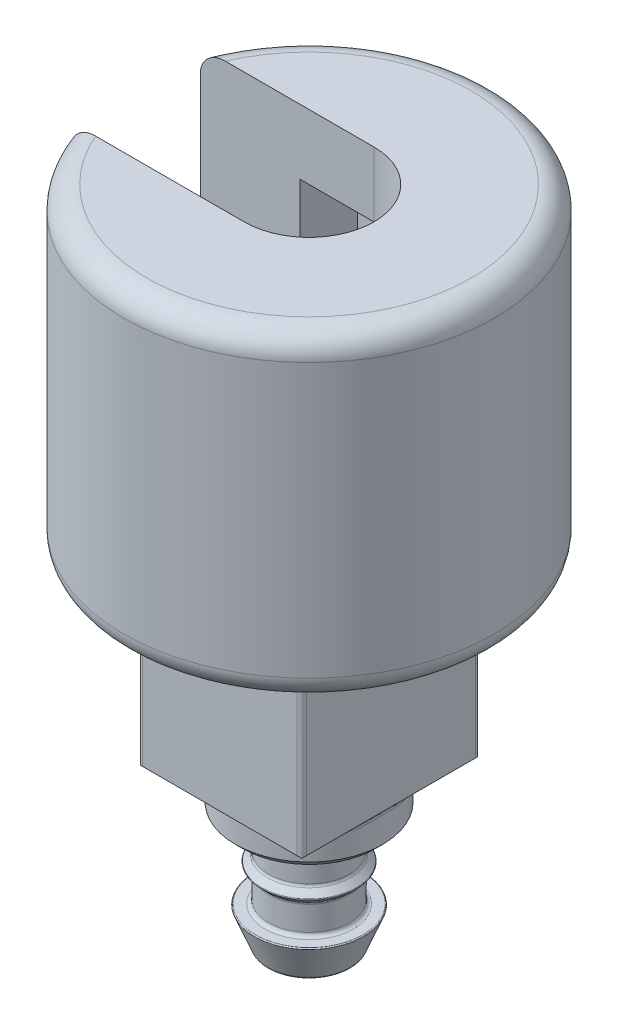
SolidWorks part; units mm, degrees
ref_plane "Front Plane" through (0, 0, 0) normal (0, 0, 1) x (1, 0, 0)
ref_plane "Top Plane" through (0, 0, 0) normal (0, 1, 0) x (1, 0, 0)
ref_plane "Right Plane" through (0, 0, 0) normal (1, 0, 0) x (0, 0, -1)
sketch "Sketch1" plane through (0, 0, 0) normal (0, 0, 1) x (1, 0, 0)
  line L0 (0, 1017.6623) -> (0, 12.7) construction
  line L1 (0, -12.7) -> (4.3656, -12.7)
  line L3 (4.3656, 0) -> (7.9375, 0)
  line L4 (7.9375, 0) -> (7.9375, 3.9688)
  line L8 (0, 3.9688) -> (0, -12.7)
  line L9 (4.3656, -12.7) -> (5.9531, -8.7312)
  line L22 (7.9375, 0) -> (7.9375, 3.9688) construction
  line L25 (7.9375, 6.35) -> (0, 6.35) construction
  line L27 (6.35, 3.9688) -> (7.9375, 3.9688)
  line L32 (5.9531, -8.7312) -> (4.3656, -8.7312)
  line L33 (4.3656, -8.7312) -> (4.3656, -5.5563)
  line L34 (4.3656, -3.9687) -> (5.1594, -4.7625)
  line L35 (5.1594, -4.7625) -> (4.3656, -5.5563)
  line L36 (5.1594, -4.7625) -> (4.3656, -4.7625) construction
  line L37 (4.3656, -3.9687) -> (4.3656, 0)
  line L38 (6.35, 3.9688) -> (0, 3.9688)
  line L40 (0, 3.9688) -> (0, -7.7377) construction
  dimension "D7" = 1.5875
  dimension "D1" = 12.7
  dimension "D2" = 3.9688
  dimension "D6" = 15.875
  dimension "D8" = 8.7312
  dimension "D10" = 7.9375
  dimension "D11" = 45
  dimension "D9" = 0.7937
revolve "Revolve1" add sketch "Sketch1" angle 360 about L0
fillet "Fillet3" radius 0.3969 5 edges at (0, -12.7, 4.3656) (0, -8.7313, 4.3656) (0, 0, 4.3656) (0, -3.9688, 4.3656) (0, -5.5562, 4.3656)
fillet "Fillet4" radius 0.0992 2 edges at (0, -8.7313, 5.9531) (0, -4.7625, 5.1594)
ref_plane "Plane1" through (0, 3.9688, 0) normal (0, 1, 0) x (1, 0, 0)
sketch "Sketch2" plane through (0, 3.9688, 0) normal (0, 1, 0) x (1, 0, 0)
  line L0 (0, 9.6273) -> (0, -9.6273) construction
  line L9 (9.0227, 0) -> (-9.0227, 0) construction
  line L11 (8.8366, 9.6273) -> (-8.8366, 9.6273)
  line L12 (8.8366, 9.6273) -> (8.8366, -9.6273)
  line L13 (8.8366, -9.6273) -> (-8.8366, -9.6273)
  line L14 (-8.8366, 9.6273) -> (-8.8366, -9.6273)
  line L15 (8.8366, 9.6273) -> (-8.8366, -9.6273) construction
  line L16 (8.8366, -9.6273) -> (-8.8366, 9.6273) construction
  point P0 (0, 0)
  point P1 (0, 0)
  point P2 (0, 0)
  point P6 (0, 0)
  point P11 (0, 0)
extrude "Boss-Extrude1" add sketch "Sketch2" along normal blind 20
sketch "Sketch3" plane through (0, -12.7, 0) normal (0, -1, 0) x (1, 0, 0)
  circle A0 centre (0, 0) radius 2.413
extrude "Cut-Extrude1" cut sketch "Sketch3" against normal blind 29
sketch "Sketch5" plane through (0, 0, 0) normal (1, 0, 0) x (0, 0, -1)
  line L0 (0, 23.9688) -> (0, 3.9688) construction
  line L1 (9.6273, 23.9688) -> (-9.6273, 23.9688) construction
  line L2 (55, 3.9688) -> (-55, 3.9688) construction
  circle A0 centre (0, 13.9688) radius 2.25
  dimension "D1" = 4.5
extrude "Cut-Extrude3" cut sketch "Sketch5" against normal blind 22.86
chamfer "Chamfer2" distance 0.762 angle 45 5 edges at (8.8366, 3.9688, 0) (0, 3.9688, -9.6273) (-8.8366, 3.9688, 0) (0, 3.9688, 9.6273) (0, 0, 7.9375)
fillet "Fillet6" radius 0.762 1 edges at (0, 3.9688, 7.9375)
sketch "Sketch7" plane through (0, 23.9688, 0) normal (0, 1, 0) x (1, 0, 0)
  circle A0 centre (0, 0) radius 20
  dimension "D1" = 40
extrude "Boss-Extrude2" add sketch "Sketch7" along normal blind 7.5
sketch "Sketch8" plane through (0, 31.4688, 0) normal (0, 1, 0) x (1, 0, 0)
  circle A0 centre (0, 0) radius 12.5
  circle A1 centre (0, 0) radius 20
  circle A2 centre (0, 0) radius 20
  dimension "D1" = 0
extrude "Boss-Extrude3" add sketch "Sketch8" along normal blind 12
ref_plane "Plane2" through (0, 43.4688, 0) normal (0, 1, 0) x (1, 0, 0)
sketch "Sketch9" plane through (0, 43.4688, 0) normal (0, 1, 0) x (1, 0, 0)
  circle A1 centre (0, 0) radius 20
  circle A2 centre (0, 0) radius 20
  dimension "D1" = 0
extrude "Boss-Extrude4" add sketch "Sketch9" along normal blind 15
sketch "Sketch10" plane through (0, 43.4688, 0) normal (0, 1, 0) x (1, 0, 0)
  line L1 (-6.5547, -10.1998) -> (5.556, -10.7764)
  line L2 (5.556, -10.7764) -> (12.1106, -0.5766)
  line L3 (12.1106, -0.5766) -> (6.5547, 10.1998)
  line L4 (6.5547, 10.1998) -> (-5.556, 10.7764)
  line L5 (-5.556, 10.7764) -> (-12.1106, 0.5766)
  line L6 (-12.1106, 0.5766) -> (-6.5547, -10.1998)
  circle A0 centre (0, 0) radius 10.5 construction
  dimension "D1" = 21
extrude "Cut-Extrude4" cut sketch "Sketch10" along normal blind 8
sketch "Sketch11" plane through (0, 0, 0) normal (1, 0, 0) x (0, 0, -1)
  line L0 (0, 58.4688) -> (0, 23.9688) construction
  line L1 (20, 58.4688) -> (-20, 58.4688) construction
  line L2 (-20, 23.9688) -> (20, 23.9688) construction
  line L3 (7, 43.4688) -> (12.5, 43.4688)
  line L5 (-7, 43.4688) -> (-7, 58.4688)
  line L6 (-7, 58.4688) -> (7, 58.4688)
  line L7 (7, 43.4688) -> (7, 58.4688)
  line L8 (-7, 43.4688) -> (7, 58.4688) construction
  line L9 (-7, 58.4688) -> (7, 43.4688) construction
  line L10 (-12.5, 33.4688) -> (12.5, 33.4688)
  line L11 (-12.5, 33.4688) -> (-12.5, 43.4688)
  line L12 (-12.5, 43.4688) -> (-7, 43.4688)
  line L13 (12.5, 33.4688) -> (12.5, 43.4688)
  line L14 (-12.5, 33.4688) -> (12.5, 43.4688) construction
  line L15 (-12.5, 43.4688) -> (12.5, 33.4688) construction
  point P6 (0, 50.9688)
  point P11 (0, 38.4688)
  dimension "D1" = 14
  dimension "D3" = 10
  dimension "D4" = 25
extrude "Cut-Extrude5" cut sketch "Sketch11" against normal through all
sketch "Sketch12" plane through (0, 58.4688, 0) normal (0, 1, 0) x (1, 0, 0)
  circle A0 centre (0, 0) radius 7
  dimension "D1" = 14
extrude "Cut-Extrude6" cut sketch "Sketch12" against normal blind 12 and the other way through all
fillet "Fillet7" radius 2.5 6 edges at (0, 23.9688, -9.6273) (8.8366, 23.9688, 0) (0, 23.9688, 9.6273) (20, 58.4687, 0) (-8.8366, 23.9688, 0) (0, 23.9688, 20)
fillet "Fillet8" radius 0.5 8 edges at (-9.5689, 23.2365, 10.3595) (9.5689, 23.2365, 10.3595) (9.5689, 23.2365, -10.3595) (-9.5689, 23.2365, -10.3595) (-8.8366, 13.0998, 9.6273) (8.8366, 13.0998, 9.6273) (8.8366, 13.0998, -9.6273) (-8.8366, 13.0998, -9.6273)
